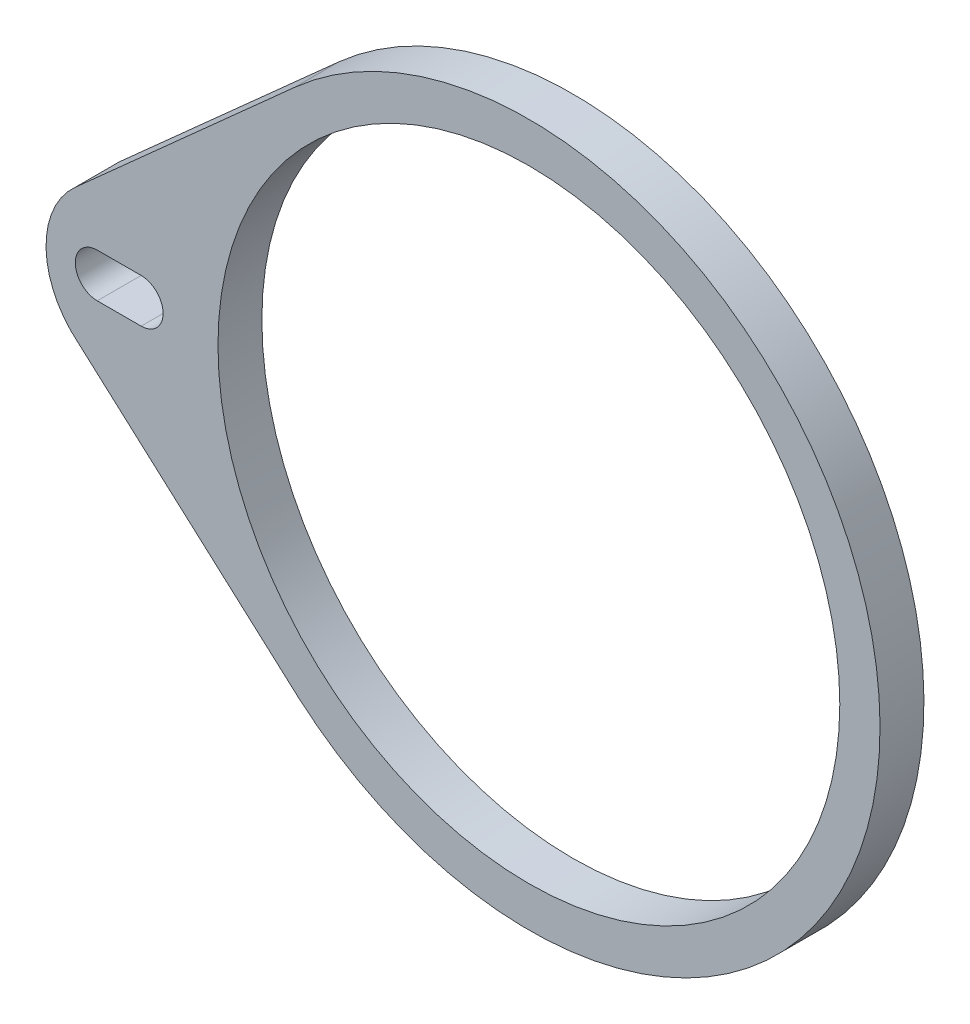
SolidWorks part; units mm, degrees
ref_plane "정면" through (0, 0, 0) normal (0, 0, 1) x (1, 0, 0)
ref_plane "윗면" through (0, 0, 0) normal (0, 1, 0) x (1, 0, 0)
ref_plane "우측면" through (0, 0, 0) normal (1, 0, 0) x (0, 0, -1)
sketch "스케치1" plane through (0, 0, 0) normal (0, 0, 1) x (1, 0, 0)
  line L0 (-22, 0) -> (0, 0) construction
  line L1 (0, 0) -> (22, 0) construction
  line L2 (-22, 0) -> (-27, 0) construction
  line L3 (-16, 17.8885) -> (-31, 4.4721)
  line L5 (-30.7569, -4.6782) -> (-15.7611, -18.0994)
  line L6 (0, 28.8675) -> (0, 0) construction
  line L7 (0, 0) -> (0, -28.8675) construction
  arc A0 (-15.7611, -18.0994) -> (-16, 17.8885) centre (0, 0) ccw
  arc A1 (-31, 4.4721) -> (-30.7569, -4.6782) centre (-27, 0) ccw
  circle A3 centre (0, 0) radius 21 construction
  dimension "D1" = 48
  dimension "D3" = 12
  dimension "D2" = 22
  dimension "D4" = 27
  dimension "D5" = 42
extrude "보스-돌출1" add sketch "스케치1" along normal blind 3
sketch "스케치2" plane through (0, 0, 0) normal (0, 0, -1) x (-1, 0, 0)
  line L0 (0, 0) -> (28, 0) construction
  line L1 (26.5, 0) -> (29.5, 0) construction
  line L2 (26.5, 1.5) -> (29.5, 1.5)
  line L4 (26.5, -1.5) -> (29.5, -1.5)
  circle A0 centre (0, 0) radius 21.25
  arc A1 (26.5, 1.5) -> (26.5, -1.5) centre (26.5, 0) ccw
  arc A2 (29.5, -1.5) -> (29.5, 1.5) centre (29.5, 0) ccw
  point P6 (28, 0)
  dimension "D1" = 42.5
  dimension "D2" = 28
  dimension "D3" = 3
  dimension "D4" = 1.5
extrude "컷-돌출1" cut sketch "스케치2" against normal blind 10
